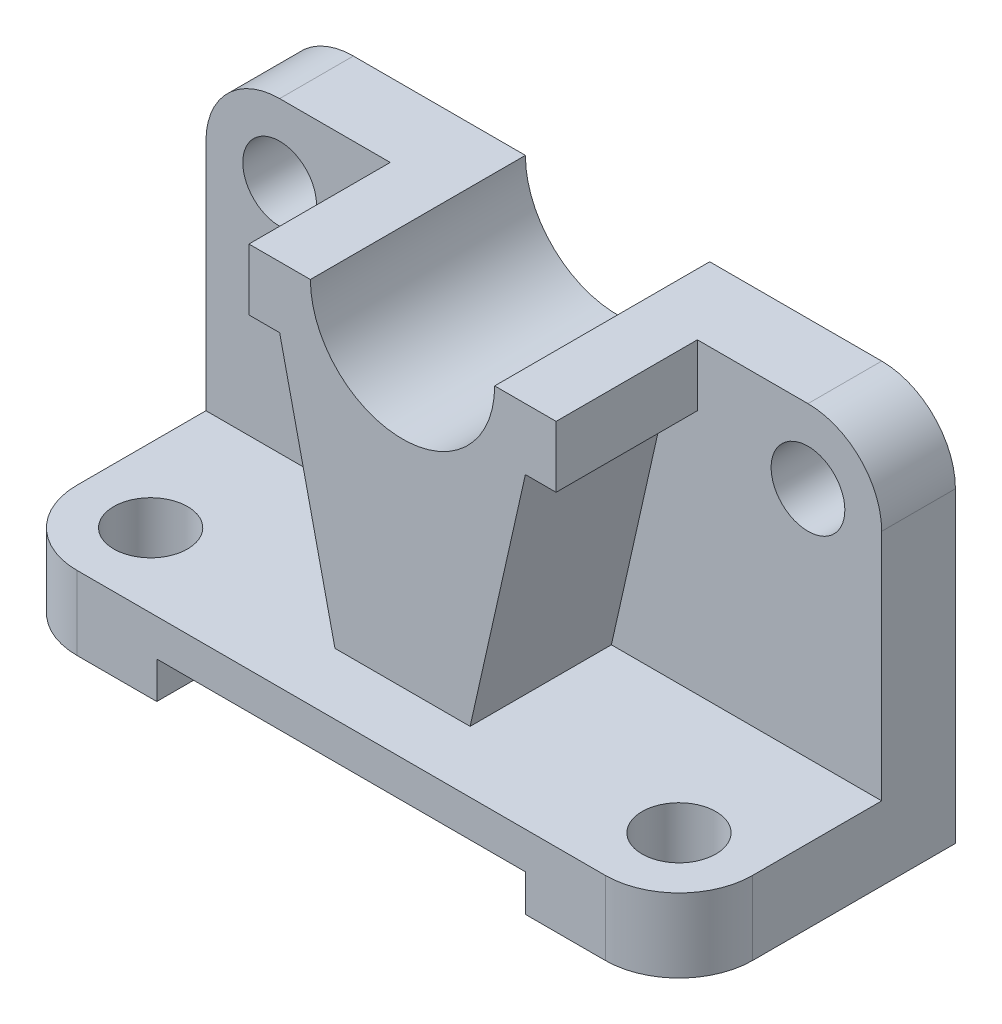
SolidWorks part; units mm, degrees
ref_plane "Front Plane" through (0, 0, 0) normal (0, 0, 1) x (1, 0, 0)
ref_plane "Top Plane" through (0, 0, 0) normal (0, 1, 0) x (1, 0, 0)
ref_plane "Right Plane" through (0, 0, 0) normal (1, 0, 0) x (0, 0, -1)
sketch "Sketch2" plane through (0, 0, 0) normal (0, 0, 1) x (1, 0, 0)
  line L0 (55, 0) -> (-55, 0)
  line L1 (-55, 0) -> (-55, 50)
  line L2 (-55, 50) -> (-15, 50)
  line L3 (55, 50) -> (55, 0)
  line L4 (-55, 0) -> (-55, -6)
  line L5 (-55, -6) -> (55, -6)
  line L6 (55, -6) -> (55, 0)
  line L7 (-55, -6) -> (-55, -12)
  line L8 (-55, -12) -> (-30, -12)
  line L9 (-30, -12) -> (-30, -6)
  line L10 (-30, -6) -> (-55, -6)
  line L11 (55, -6) -> (55, -12)
  line L12 (55, -12) -> (30, -12)
  line L13 (30, -12) -> (30, -6)
  line L14 (30, -6) -> (55, -6)
  line L15 (11, 0) -> (-11, 0)
  line L16 (-11, 0) -> (-20, 40)
  line L17 (-20, 40) -> (-25, 40)
  line L18 (-25, 40) -> (-25, 50)
  line L19 (-25, 50) -> (-15, 50)
  line L20 (25, 50) -> (25, 40)
  line L21 (25, 40) -> (20, 40)
  line L22 (20, 40) -> (11, 0)
  line L23 (-25, 50) -> (-15, 50)
  line L24 (-25, 50) -> (-15, 50)
  line L25 (15, 50) -> (55, 50)
  line L26 (15, 50) -> (25, 50)
  line L27 (15, 50) -> (25, 50)
  line L28 (0, 0) -> (0, 67.8411) construction
  arc A0 (-15, 50) -> (15, 50) centre (0, 50) ccw
  circle A1 centre (-43, 38) radius 6
  circle A2 centre (43, 38) radius 6
  point P4 (0, 0)
  point P17 (0, 0)
  dimension "D13" = 30
  dimension "D10" = 12
  dimension "D1" = 110
  dimension "D2" = 60
  dimension "D3" = 25
  dimension "D4" = 6
  dimension "D5" = 6
  dimension "D6" = 12
  dimension "D7" = 50
  dimension "D8" = 22
  dimension "D9" = 50
  dimension "D11" = 10
  dimension "D12" = 10
  dimension "D14" = 12
  dimension "D15" = 12
extrude "Boss-Extrude2" add sketch "Sketch2" along normal blind 45 contours L13 L12 L11 L5 | L8 L9 L5 L7 | L5 L6 L0 L15 L4 region at (0, -3, 0) region at (42.5, -9, 0) region at (-42.5, -9, 0)
extrude "Boss-Extrude3" add sketch "Sketch2<4>" along normal blind 35 contours L28 L0 L22 L21 L20 L25 A0 | L15 L28 A0 L2 L18 L17 L16 region at (10.0103, 24.7218, 0) region at (-10.0103, 24.7218, 0)
sketch "Sketch2<4>" plane through (0, 0, 0) normal (0, 0, 1) x (1, 0, 0) same geometry as "Sketch2"
extrude "Boss-Extrude4" add sketch "Sketch2<5>" along normal blind 12 contours L25 L20 L21 L22 L0 L3 A2 | L17 L18 L2 L1 L0 L16 A1 region at (35.484, 22.4134, 0) region at (-35.484, 22.4134, 0)
sketch "Sketch2<5>" plane through (0, 0, 0) normal (0, 0, 1) x (1, 0, 0) same geometry as "Sketch2"
fillet "Fillet1" radius 12 4 edges at (55, -6, 45) (-55, -6, 45) (-55, 50, 6) (55, 50, 6)
sketch "Sketch3" plane through (0, 0, 0) normal (0, 1, 0) x (1, 0, 0)
  line L0 (-55, -33) -> (-55, -12) construction
  line L1 (43, -45) -> (-43, -45) construction
  line L2 (0, 0) -> (0, -51.7634) construction
  circle A0 centre (-43, -33) radius 6
  circle A1 centre (43, -33) radius 6
  dimension "D1" = 12
  dimension "D2" = 12
  dimension "D3" = 12
extrude "Cut-Extrude1" cut sketch "Sketch3" against normal through all both and the other way through all
